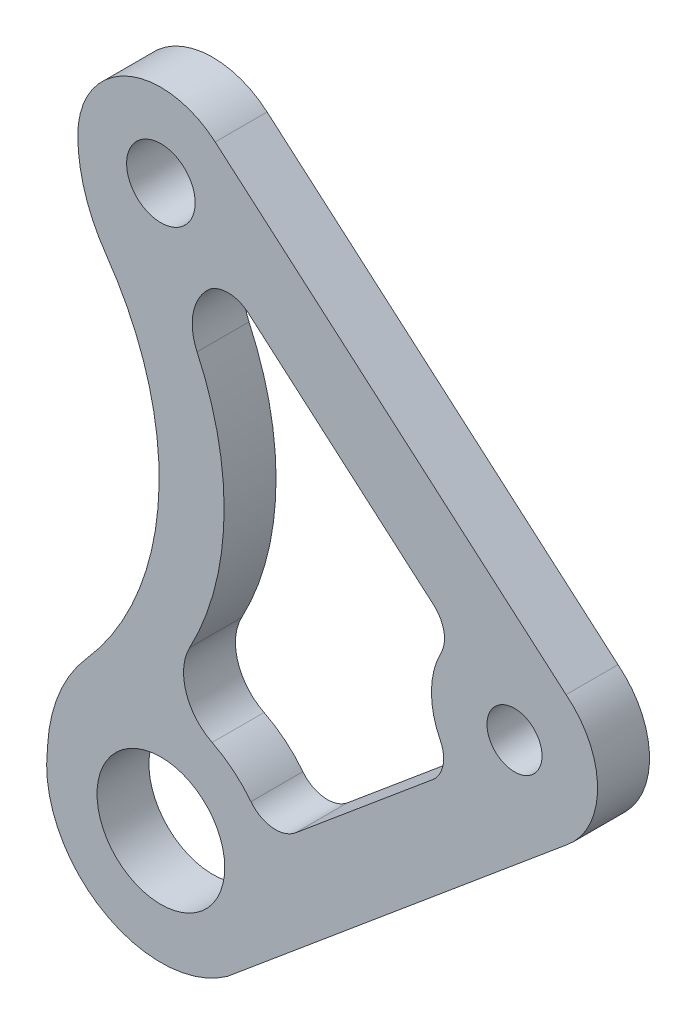
SolidWorks part; units mm, degrees
material "6061-T6 (SS)"
ref_plane "X-Y Datum" through (0, 0, 0) normal (0, 0, 1) x (1, 0, 0)
ref_plane "X-Z Datum" through (0, 0, 0) normal (0, 1, 0) x (1, 0, 0)
ref_plane "Y-Z Datum" through (0, 0, 0) normal (1, 0, 0) x (0, 0, -1)
sketch "Sketch1" plane through (0, 0, 0) normal (0, 0, 1) x (1, 0, 0)
  line L0 (0, 0) -> (0, 68.58) construction
  line L1 (0, 68.58) -> (43.2483, 31.2208) construction
  line L2 (43.2483, 31.2208) -> (0, 0) construction
  line L3 (-13.97, 0) -> (-10.16, 68.58)
  line L4 (6.6414, 76.2688) -> (49.5557, 39.1859)
  line L5 (49.5557, 23.2558) -> (8.1778, -11.3263)
  circle A0 centre (0, 0) radius 7.8105
  circle A1 centre (43.2483, 31.2208) radius 3.3655
  circle A2 centre (0, 68.58) radius 4.191
  arc A3 (-10.16, 68.58) -> (6.6414, 76.2688) centre (0, 68.58) cw
  arc A4 (49.5557, 39.1859) -> (49.5557, 23.2558) centre (43.2483, 31.2208) cw
  arc A5 (8.1778, -11.3263) -> (-13.97, 0) centre (0, 0) cw
  point P16 (53.4083, 31.2208)
  dimension "D4" = 15.621
  dimension "D5" = 6.731
  dimension "D6" = 8.382
  dimension "D7" = 13.97
  dimension "D8" = 10.16
  dimension "D9" = 10.16
  dimension "D1" = 68.58
  dimension "D2" = 57.15
  dimension "D3" = 53.34
  dimension "D10" = 130.82
  dimension "D11" = 125.83
  dimension "D12" = 103.25
extrude "Boss-Extrude1" add sketch "Sketch1" along normal blind 6.35
sketch "Sketch2" plane through (0, 0, 6.35) normal (0, 0, 1) x (1, 0, 0)
  line L0 (-10.16, 68.58) -> (-13.97, 0) construction
  line L1 (-10.5128, 62.23) -> (-13.4408, 9.525)
  arc A0 (-10.5128, 62.23) -> (-13.4408, 9.525) centre (-35.7711, 37.1994) cw
  dimension "D3" = 35.56
  dimension "D1" = 6.35
  dimension "D2" = 9.525
extrude "Cut-Extrude1" cut sketch "Sketch2" against normal blind 6.35
fillet "Fillet1" radius 19.05 2 edges at (-10.5128, 62.23, 3.175) (-13.4408, 9.525, 3.175)
sketch "Sketch3" plane through (0, 0, 6.35) normal (0, 0, 1) x (1, 0, 0)
  line L2 (8.0877, 62.4306) -> (35.9845, 38.3245)
  line L3 (49.5557, 39.1859) -> (6.6414, 76.2688) construction
  line L6 (12.9992, 5.1168) -> (35.8725, 24.2335)
  arc A0 (35.9845, 38.3245) -> (35.8725, 24.2335) centre (43.2483, 31.2208) ccw
  arc A1 (-1.655, 13.8716) -> (12.9992, 5.1168) centre (0, 0) cw
  arc A3 (1.2017, 58.4913) -> (-1.655, 13.8716) centre (-27.8241, 37.9483) cw
  arc A6 (1.2017, 58.4913) -> (8.0877, 62.4306) centre (0, 68.58) ccw
  dimension "D1" = 10.16
  dimension "D2" = 10.16
  dimension "D3" = 13.97
  dimension "D6" = 6.7275
  dimension "D7" = 35.56
  dimension "D4" = 29.81
  dimension "D5" = 9.525
  dimension "D11" = 75.318
extrude "Cut-Extrude2" cut sketch "Sketch3" against normal blind 6.35
sketch3d "3DSketch1"
  line L0 (0, 68.58, 6.35) -> (0, 68.58, 0) construction
  line L1 (43.2483, 31.2208, 6.35) -> (43.2483, 31.2208, 0) construction
  point P0 (0, 68.58, 6.35)
  point P1 (43.2483, 31.2208, 6.35)
fillet "Fillet2" radius 3.81 4 edges at (35.9845, 38.3245, 3.175) (12.9992, 5.1168, 3.175) (35.8725, 24.2335, 3.175) (8.0877, 62.4306, 3.175)
fillet "Fillet4" radius 6.35 2 edges at (1.2017, 58.4913, 3.175) (-1.655, 13.8716, 3.175)
